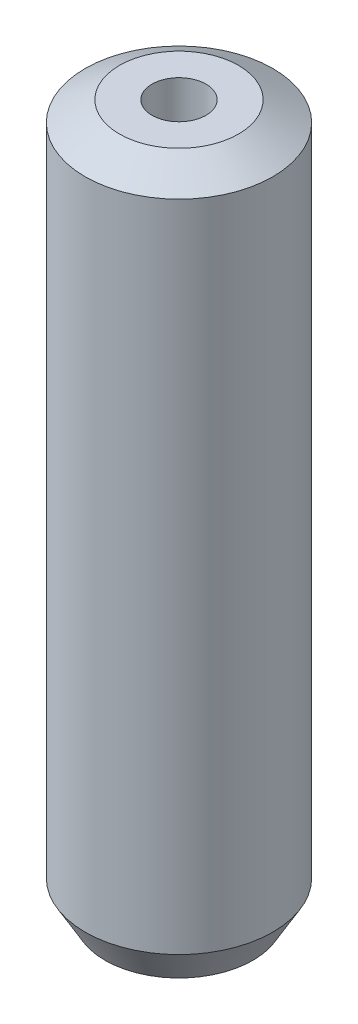
SolidWorks part; units mm, degrees
ref_plane "Front Plane" through (0, 0, 0) normal (0, 0, 1) x (1, 0, 0)
ref_plane "Top Plane" through (0, 0, 0) normal (0, 1, 0) x (1, 0, 0)
ref_plane "Right Plane" through (0, 0, 0) normal (1, 0, 0) x (0, 0, -1)
sketch "Sketch1" plane through (0, 0, 0) normal (0, 1, 0) x (1, 0, 0)
  circle A0 centre (0, 0) radius 5
  dimension "SHAFT_OD" = 10
extrude "Boss-Extrude1" add sketch "Sketch1" along normal blind 37.7509
sketch "Sketch2" plane through (0, 0, 0) normal (0, 1, 0) x (1, 0, 0)
  circle A0 centre (0, 0) radius 1.4406
  dimension "BORE_D" = 2.8812
extrude "Cut-Extrude1" cut sketch "Sketch2" along normal through all
chamfer "Chamfer1" distance 1.0557 angle 60 2 edges at (0, 37.7509, 5) (0, 0, 5) first distance on face at (0, 37.7509, 5) first distance on face at (0, 0, 1.4406)
